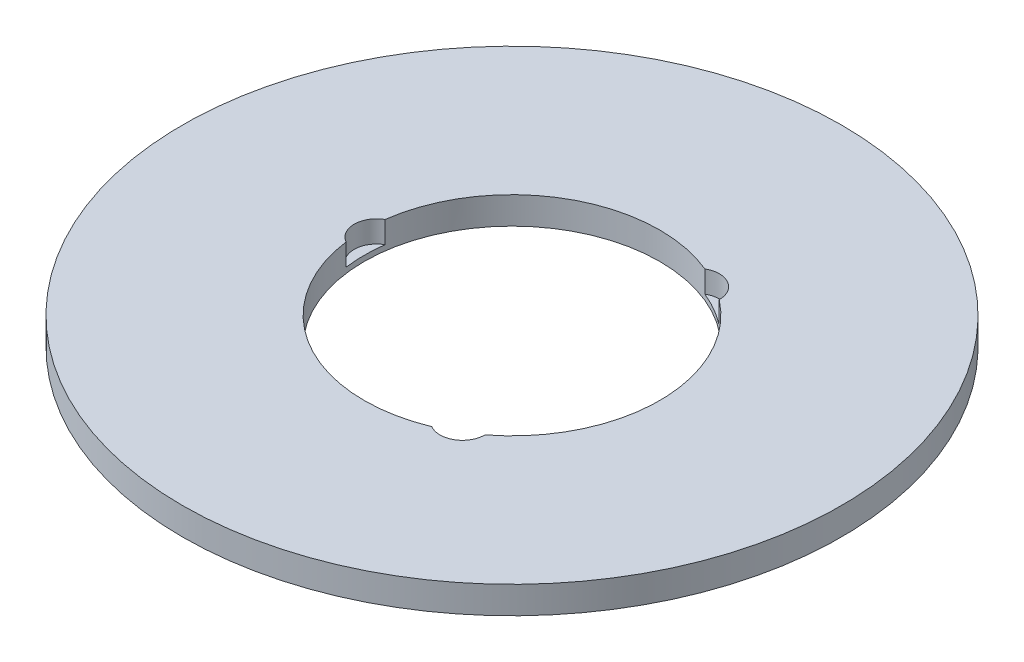
SolidWorks part; units mm, degrees
ref_plane "Front Plane" through (0, 0, 0) normal (0, 0, 1) x (1, 0, 0)
ref_plane "Top Plane" through (0, 0, 0) normal (0, 1, 0) x (1, 0, 0)
ref_plane "Right Plane" through (0, 0, 0) normal (1, 0, 0) x (0, 0, -1)
sketch "Sketch1" plane through (0, 0, 0) normal (0, 1, 0) x (1, 0, 0)
  circle A0 centre (0, 0) radius 72.5
  dimension "FLANGE_OD" = 145
extrude "Boss-Extrude1" add sketch "Sketch1" along normal blind 6
sketch "Sketch2" plane through (0, 0, 0) normal (0, 1, 0) x (1, 0, 0)
  circle A0 centre (0, 0) radius 32.5
  dimension "BORE_D" = 65
extrude "Cut-Extrude1" cut sketch "Sketch2" along normal through all
sketch "Sketch3" plane through (0, 6, 0) normal (0, 1, 0) x (1, 0, 0)
  circle A0 centre (0, 0) radius 29.7952 construction
  circle A1 centre (-29.7952, 0) radius 4.92
  dimension "BOLT_D" = 9.8401
  dimension "BOLT_PCD" = 59.5905
extrude "Cut-Extrude2" cut sketch "Sketch3" against normal blind 4.8045
pattern_circular "CirPattern1" count 3 over 360 about axis through (0, 0, 0) along (0, 1, 0) of "Cut-Extrude2"
